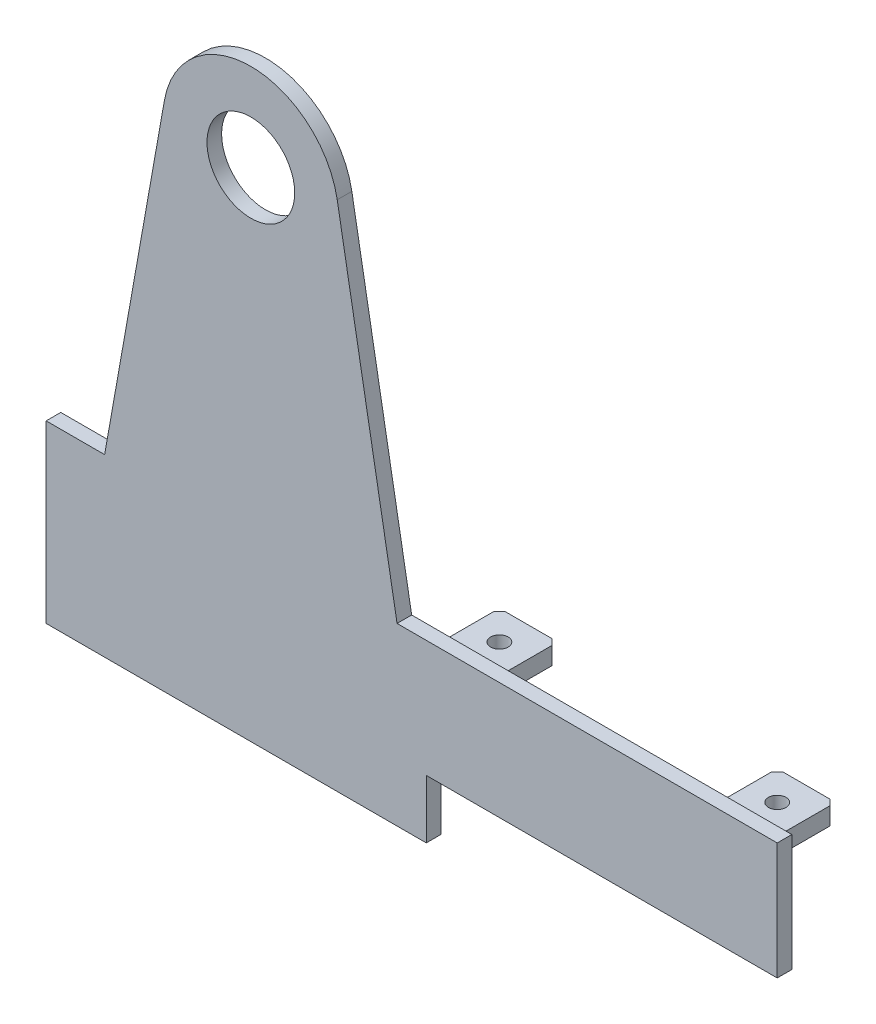
SolidWorks part; units mm, degrees
material "Сталь 3 ГОСТ 535-88"
ref_plane "Спереди" through (0, 0, 0) normal (0, 0, 1) x (1, 0, 0)
ref_plane "Сверху" through (0, 0, 0) normal (0, 1, 0) x (1, 0, 0)
ref_plane "Справа" through (0, 0, 0) normal (1, 0, 0) x (0, 0, -1)
sketch "Эскиз1" plane through (0, 0, 0) normal (0, 0, 1) x (1, 0, 0)
  line L0 (-65, 0) -> (-65, 60)
  line L1 (-65, 60) -> (185, 60)
  line L2 (185, 60) -> (185, 20)
  line L3 (185, 20) -> (65, 20)
  line L4 (65, 20) -> (65, 0)
  line L6 (65, 0) -> (-65, 0)
  dimension "D1" = 130
  dimension "D2" = 60
  dimension "D3" = 40
  dimension "D4" = 250
extrude "Бобышка-Вытянуть1" add sketch "Эскиз1" against normal blind 5
sketch "Эскиз2" plane through (0, 0, 0) normal (0, 0, 1) x (1, 0, 0)
  line L0 (-45, 60) -> (-24.538, 175.2446)
  line L1 (185, 60) -> (-65, 60) construction
  line L2 (34.538, 175.2446) -> (55, 60)
  line L3 (-45, 60) -> (55, 60)
  line L4 (5, 204.1229) -> (5, 138.6821) construction
  arc A0 (-24.538, 175.2446) -> (34.538, 175.2446) centre (5, 170) cw
  circle A1 centre (5, 170) radius 15
  point P12 (5, 60)
  dimension "D2" = 30
  dimension "D4" = 30
  dimension "D1" = 20
  dimension "D3" = 140
  dimension "D5" = 100
extrude "Бобышка-Вытянуть2" add sketch "Эскиз2" against normal up to surface (5 mm away) up to face at (61.6667, 26.6667, -5)
ref_plane "Плоскость1" through (0, 57, 0) normal (0, 1, 0) x (1, 0, 0)
sketch "Эскиз3" plane through (0, 57, 0) normal (0, 1, 0) x (1, 0, 0)
  line L7 (185, 5) -> (185, 0) construction
  line L8 (185, 5) -> (55, 5) construction
  line L9 (180, 5) -> (160, 5)
  line L10 (180, 5) -> (180, 25)
  line L11 (180, 25) -> (160, 25)
  line L12 (160, 5) -> (160, 25)
  line L13 (170, 25) -> (170, 5) construction
  line L14 (180, 15) -> (160, 15) construction
  circle A1 centre (170, 15) radius 3
  dimension "D2" = 6
  dimension "D1" = 20
  dimension "D3" = 15
extrude "Бобышка-Вытянуть3" add sketch "Эскиз3" against normal blind 6 separate body
ref_plane "Плоскость2" through (60, 0, 0) normal (1, 0, 0) x (0, 0, -1)
chamfer "Фаска1" distance 2 angle 45 4 edges at (160, 54, -5) (160, 54, -25) (180, 54, -25) (180, 54, -5)
sketch "Эскиз4" plane through (0, 57, 0) normal (0, 1, 0) x (1, 0, 0)
  line L0 (185, 5) -> (55, 5) construction
  line L1 (65, 5) -> (85, 5)
  line L2 (65, 5) -> (65, 25)
  line L3 (65, 25) -> (85, 25)
  line L4 (85, 5) -> (85, 25)
  line L5 (75, 25) -> (75, 5) construction
  line L6 (65, 15) -> (85, 15) construction
  line L8 (160, 23) -> (160, 7) construction
  circle A0 centre (75, 15) radius 3
  point P0 (75, 15)
  dimension "D3" = 6
  dimension "D1" = 20
  dimension "D2" = 75
extrude "Бобышка-Вытянуть4" add sketch "Эскиз4" against normal blind 6 separate body
chamfer "Фаска2" distance 2 angle 45 4 edges at (85, 54, -5) (65, 54, -5) (85, 54, -25) (65, 54, -25)
